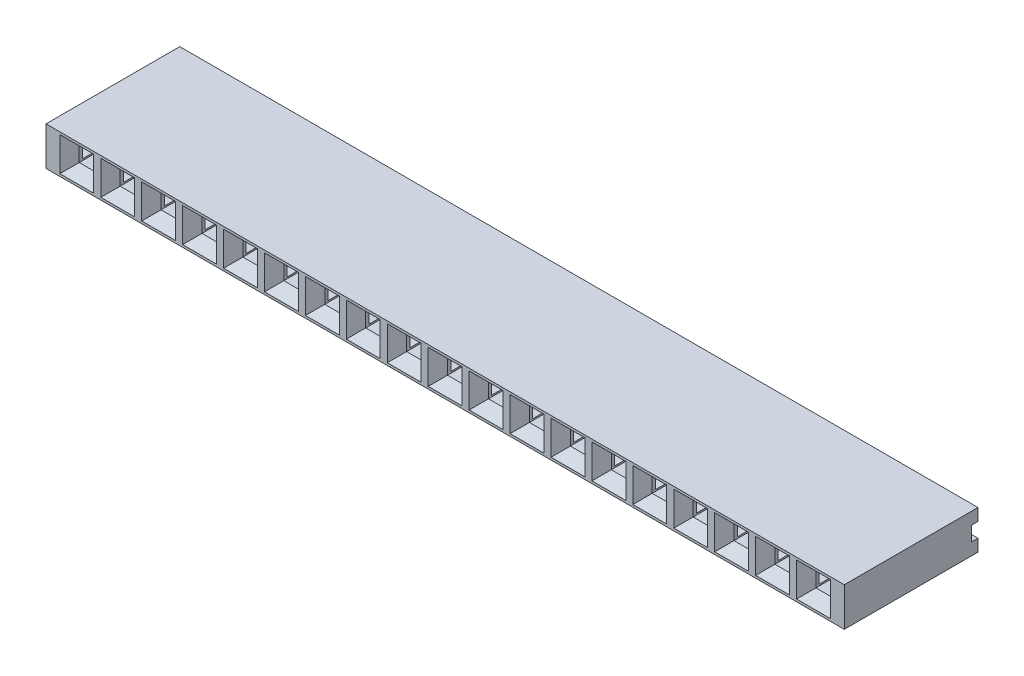
SolidWorks part; units mm, degrees
note: The reader was unsure of these and kept them because the rebuilt part matched: shared geometry of "Эскиз-БоковаяНакладка<2>".
other "Пластик"
ref_plane "Front Plane" through (0, 0, 0) normal (0, 0, 1) x (1, 0, 0)
ref_plane "Top Plane" through (0, 0, 0) normal (0, 1, 0) x (1, 0, 0)
ref_plane "Right Plane" through (0, 0, 0) normal (1, 0, 0) x (0, 0, -1)
sketch "Эскиз-ВнутреннееСечение" plane through (0, 0, 0) normal (0, 0, 1) x (1, 0, 0)
  line L0 (-1, 0.35) -> (-0.45, 0.35)
  line L1 (-1.27, -1.2) -> (1.27, -1.2)
  line L2 (-1.27, -1.2) -> (-1.27, 1.2)
  line L3 (-1.27, 1.2) -> (1.27, 1.2)
  line L4 (1.27, -1.2) -> (1.27, 1.2)
  line L5 (-1.27, -1.2) -> (1.27, 1.2) construction
  line L6 (-1.27, 1.2) -> (1.27, -1.2) construction
  line L8 (-1, -0.35) -> (-1, 0.35)
  line L9 (-0.45, 0.45) -> (0.45, 0.45)
  line L11 (0, 1.2) -> (0, -1.2) construction
  line L12 (0.45, 0.35) -> (0.45, 0.45)
  line L13 (-1.27, 0) -> (1.27, 0) construction
  line L14 (1, 0.35) -> (0.45, 0.35)
  line L15 (-0.45, 0.35) -> (-0.45, 0.45)
  line L16 (1, -0.35) -> (0.45, -0.35)
  line L17 (0.45, -0.35) -> (0.45, -0.45)
  line L18 (-0.45, -0.35) -> (-0.45, -0.45)
  line L19 (-1, -0.35) -> (-0.45, -0.35)
  line L20 (-0.45, -0.45) -> (0.45, -0.45)
  line L21 (1, -0.35) -> (1, 0.35)
  point P0 (0, 0)
  point P5 (0, 0)
  dimension "D1" = 2.4
  dimension "D2" = 2.54
  dimension "D3" = 1
  dimension "D4" = 0.35
  dimension "D5" = 0.1
  dimension "D7" = 0.55
extrude "Бобышка-ОтЦентраВверхВниз" add sketch "Эскиз-ВнутреннееСечение" against normal blind 0.4 and the other way blind 6.7 contours L8 L0 L15 L9 L12 L14 L21 L16 L17 L20 L18 L19
sketch "Эскиз-СамыйНиз" plane through (0, 0, -0.4) normal (0, 0, -1) x (-1, 0, 0)
  line L1 (1.27, 1.2) -> (1.27, -1.2) construction
  line L2 (-1.27, -1.2) -> (-1.27, 1.2) construction
  line L3 (0.45, -0.45) -> (-0.45, -0.45) construction
  line L4 (1.27, -1.2) -> (-1.27, -1.2)
  line L5 (1.27, -1.2) -> (1.27, -0.45)
  line L6 (1.27, -0.45) -> (-1.27, -0.45)
  line L7 (-1.27, -1.2) -> (-1.27, -0.45)
  line L9 (-1.27, 1.2) -> (1.27, 1.2)
  line L10 (-1.27, 1.2) -> (-1.27, 0.45)
  line L11 (-1.27, 0.45) -> (1.27, 0.45)
  line L12 (1.27, 1.2) -> (1.27, 0.45)
  line L13 (-0.45, 0.45) -> (0.45, 0.45) construction
extrude "Бобышка-СамыйНиз" add sketch "Эскиз-СамыйНиз" along normal blind 0.4
sketch "Эскиз-ВерхняяПеремычка" plane through (0, 0, 6.7) normal (0, 0, 1) x (1, 0, 0)
  line L1 (-1.27, 1.2) -> (1.27, 1.2)
  line L2 (-1.27, 1.2) -> (-1.27, -1.2)
  line L3 (-1.27, -1.2) -> (1.27, -1.2)
  line L4 (1.27, 1.2) -> (1.27, -1.2)
  line L5 (-0.45, -0.45) -> (0.45, -0.45)
  line L6 (-0.45, -0.45) -> (-0.45, 0.45)
  line L7 (-0.45, 0.45) -> (0.45, 0.45)
  line L8 (0.45, -0.45) -> (0.45, 0.45)
  line L9 (-0.45, -0.45) -> (0.45, 0.45) construction
  line L10 (-0.45, 0.45) -> (0.45, -0.45) construction
  point P4 (0, 0)
extrude "Бобышка-СамыйВерх" add sketch "Эскиз-ВерхняяПеремычка" along normal blind 0.8
chamfer "Фаска-СверхуВнутрь" distance 0.6 angle 45 4 edges at (0, -0.45, 7.5) (0.45, 0, 7.5) (0, 0.45, 7.5) (-0.45, 0, 7.5)
pattern_linear "Пластик_Массив" count 19 spacing 2.54 along (-1, 0, 0) of bodies 103
combine bodies "Соединить_Массив" operation type add bodies to combine 103 120 119 118 117 116 115 114 113 112 111 110 109 108 107 106 105 104 121
sketch "Эскиз-БоковаяНакладка" plane through (1.27, 0, 0) normal (1, 0, 0) x (0, 0, -1)
  line L1 (0.8, 1.2) -> (0.8, 0.45)
  line L2 (0.8, 0.45) -> (0.4, 0.45)
  line L3 (0.4, 0.45) -> (0.4, -0.45)
  line L4 (0.4, -0.45) -> (0.4, 0.45) construction
  line L5 (0.4, -0.45) -> (0.8, -0.45)
  line L6 (0.8, -0.45) -> (0.8, -1.2)
  line L7 (0.8, -1.2) -> (-7.5, -1.2)
  line L8 (-7.5, -1.2) -> (-7.5, 1.2)
  line L9 (-7.5, 1.2) -> (0.8, 1.2)
extrude "Бобышка-БоковаяНакладка1" add sketch "Эскиз-БоковаяНакладка" along normal blind 0.64 from surface at 0 starting at face at (1.27, 0, 1.375)
extrude "Бобышка-БоковаяНакладка2" add sketch "Эскиз-БоковаяНакладка<2>" against normal blind 0.64 from surface
sketch "Эскиз-БоковаяНакладка<2>" plane through (1.27, 0, 0) normal (1, 0, 0) x (0, 0, -1) same geometry as "Эскиз-БоковаяНакладка"
